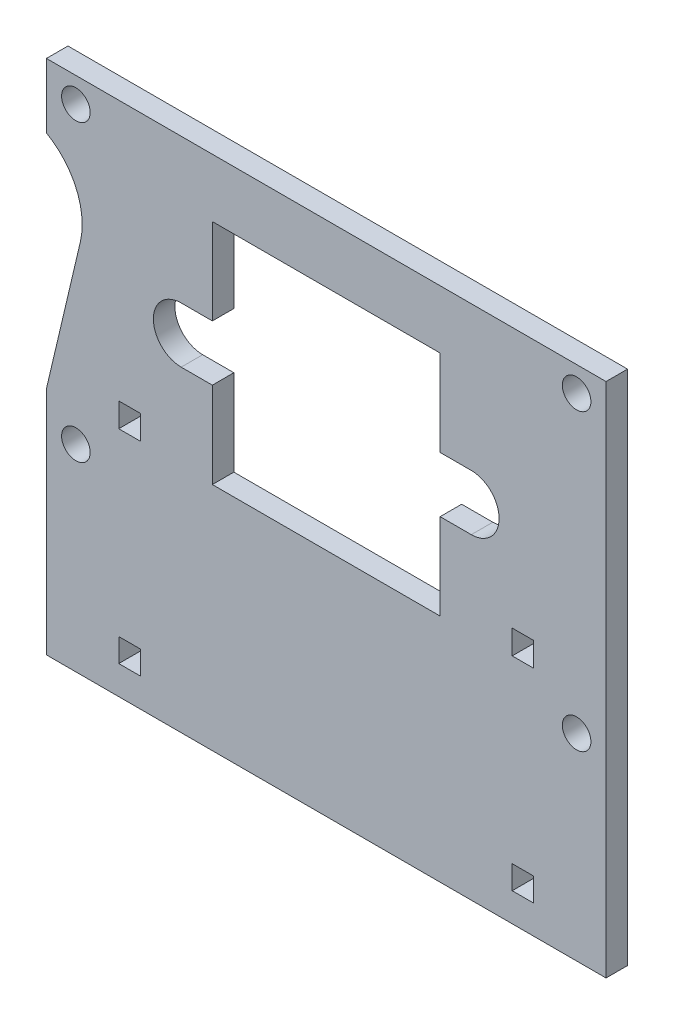
SolidWorks part; units mm, degrees
material "Beech"
ref_plane "Front Plane" through (0, 0, 0) normal (0, 0, 1) x (1, 0, 0)
ref_plane "Top Plane" through (0, 0, 0) normal (0, 1, 0) x (1, 0, 0)
ref_plane "Right Plane" through (0, 0, 0) normal (1, 0, 0) x (0, 0, -1)
sketch "Sketch1" plane through (0, 0, 0) normal (0, 0, 1) x (1, 0, 0)
  line L0 (-20.6375, 0) -> (20.6375, 0)
  line L1 (-20.6375, 17) -> (-18.1395, 27.6149)
  line L2 (13.716, 3.8411) -> (13.716, 2.1139)
  line L3 (-15.3035, 3.8411) -> (-13.716, 3.8411)
  line L4 (-15.3035, 3.8411) -> (-15.3035, 2.1139)
  line L5 (-15.3035, 2.1139) -> (-13.716, 2.1139)
  line L6 (-13.716, 3.8411) -> (-13.716, 2.1139)
  line L7 (15.3035, 2.1139) -> (13.716, 2.1139)
  line L8 (15.3035, 3.8411) -> (15.3035, 2.1139)
  line L9 (15.3035, 3.8411) -> (13.716, 3.8411)
  line L14 (15.3035, 17.1139) -> (15.3035, 18.8919)
  line L15 (13.716, 17.1139) -> (15.3035, 17.1139)
  line L16 (13.716, 18.8919) -> (13.716, 17.1139)
  line L17 (15.3035, 18.8919) -> (13.716, 18.8919)
  line L18 (15.3035, 17.1139) -> (15.3035, 18.8919)
  line L19 (13.716, 17.1139) -> (15.3035, 17.1139)
  line L20 (13.716, 18.8919) -> (13.716, 17.1139)
  line L21 (15.3035, 18.8919) -> (13.716, 18.8919)
  line L22 (-13.716, 17.1139) -> (-13.716, 18.8919)
  line L23 (-15.3035, 17.1139) -> (-13.716, 17.1139)
  line L24 (-15.3035, 18.8919) -> (-15.3035, 17.1139)
  line L25 (-13.716, 18.8919) -> (-15.3035, 18.8919)
  line L26 (-13.716, 17.1139) -> (-13.716, 18.8919)
  line L27 (-15.3035, 17.1139) -> (-13.716, 17.1139)
  line L28 (-15.3035, 18.8919) -> (-15.3035, 17.1139)
  line L29 (-13.716, 18.8919) -> (-15.3035, 18.8919)
  line L44 (0, 14.605) -> (0, 24.13) construction
  line L45 (-8.4, 23.35) -> (-8.4, 17)
  line L46 (-20.6375, 0) -> (-20.6375, 38.1)
  line L47 (-20.6375, 38.1) -> (20.6375, 38.1)
  line L48 (20.6375, 0) -> (20.6375, 38.1)
  line L49 (-20.6375, 25.4) -> (20.6375, 25.4) construction
  line L50 (8.4, 33.8) -> (-8.4, 33.8)
  line L60 (8.4, 33.8) -> (8.4, 27.45)
  line L61 (8.4, 17) -> (-8.4, 17)
  line L62 (-8.4, 33.8) -> (-8.4, 27.45)
  line L63 (8.4, 33.8) -> (-8.4, 17) construction
  line L64 (8.4, 17) -> (-8.4, 33.8) construction
  line L66 (-8.4, 23.35) -> (-10.7, 23.35)
  line L67 (8.4, 23.35) -> (10.7, 23.35)
  line L68 (-8.4, 27.45) -> (-10.7, 27.45)
  line L69 (8.4, 27.45) -> (10.7, 27.45)
  line L71 (8.4, 23.35) -> (8.4, 17)
  arc A0 (-10.7, 23.35) -> (-10.7, 27.45) centre (-10.7, 25.4) cw
  arc A1 (10.7, 23.35) -> (10.7, 27.45) centre (10.7, 25.4) ccw
  circle A2 centre (-18.4658, 36.2585) radius 1.0541
  circle A3 centre (-18.4658, 14.5415) radius 1.0541
  circle A4 centre (18.4658, 14.5415) radius 1.0541
  circle A5 centre (18.4658, 36.2585) radius 1.0541
  arc A6 (-20.6375, 33.337) -> (-18.1395, 27.6149) centre (-23.2092, 28.808) cw
  point P0 (0, 0)
  point P56 (0, 25.4)
  point P60 (0, 38.1)
  dimension "D14" = 12.7
  dimension "D4" = 2.1082
  dimension "D3" = 38.1
  dimension "D9" = 13.716
  dimension "D10" = 0
  dimension "D11" = 0
  dimension "D12" = 41.275
  dimension "D15" = 16.8
  dimension "D19" = 16.8
  dimension "D20" = 4.1
  dimension "D21" = 2.3
  dimension "D5" = 2.1717
  dimension "D6" = 1.8415
  dimension "D7" = 1.7272
  dimension "D8" = 1.5875
extrude "Boss-Extrude1" add sketch "Sketch1" along normal blind 1.5875 contours L48 L47 L46 L69 region at (-20.0758, 8.5, 0)
fillet "Fillet7" [suppressed] radius 15.24
